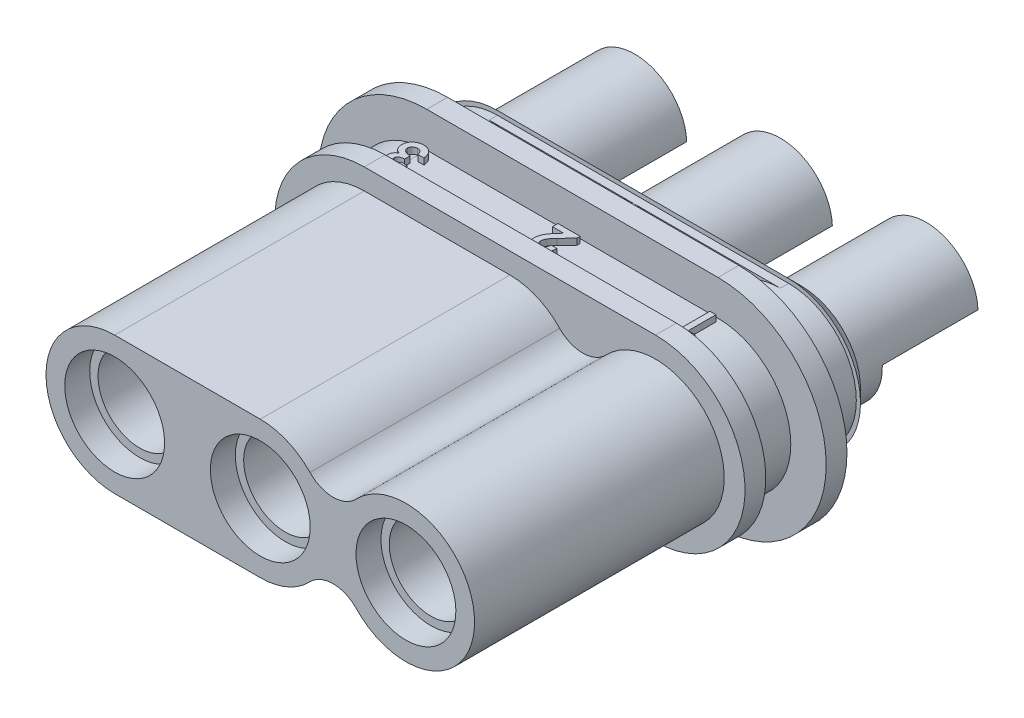
SolidWorks part; units mm, degrees
material "PA Type 6"
ref_plane "Front" through (0, 0, 0) normal (0, 0, 1) x (1, 0, 0)
ref_plane "Top" through (0, 0, 0) normal (0, 1, 0) x (1, 0, 0)
ref_plane "Side" through (0, 0, 0) normal (1, 0, 0) x (0, 0, -1)
ref_axis "Axis1" through (0, 0, 54.75) along (0, 0, -1)
sketch "Sketch1" plane through (0, 0, 0) normal (0, 0, 1) x (1, 0, 0)
  line L0 (-3.5, 0) -> (3.5, 0) construction
  line L1 (6.05, 0) -> (-6.05, 0) construction
  line L2 (-3.5, 1.65) -> (3.5, 1.65)
  line L3 (-3.5, -1.65) -> (3.5, -1.65)
  arc A0 (-3.5, 1.65) -> (-3.5, -1.65) centre (-3.5, 0) ccw
  arc A1 (3.5, -1.65) -> (3.5, 1.65) centre (3.5, 0) ccw
  point P5 (0, 0)
  dimension "D2" = 7
  dimension "D1" = 3.3
extrude "Boss-Extrude1" add sketch "Sketch1" along normal blind 6
sketch "Sketch2" plane through (0, 0, 0) normal (0, 0, 1) x (1, 0, 0)
  circle A0 centre (3.5, 0) radius 1.25
  circle A1 centre (0, 0) radius 1.25
  circle A2 centre (-3.5, 0) radius 1.25
  dimension "D1" = 2.5
sketch "Sketch3" plane through (0, 0, 6) normal (0, 0, 1) x (1, 0, 0)
  line L0 (3.5, 1.65) -> (-3.5, 1.65) construction
  line L1 (3.5, 1.65) -> (0, 1.65)
  line L2 (3.3, 0) -> (-3.3, 0) construction
  line L3 (0, 0) -> (7.6068, 0) construction
  line L4 (3.5, -1.65) -> (0, -1.65)
  arc A0 (3.5, 1.65) -> (2.3052, 1.1379) centre (3.5, 0) ccw
  arc A2 (1.1948, 1.1379) -> (0, 1.65) centre (0, 0) ccw
  arc A3 (1.1948, 1.1379) -> (2.3052, 1.1379) centre (1.75, 1.6667) ccw
  arc A4 (1.1948, -1.1379) -> (2.3052, -1.1379) centre (1.75, -1.6667) cw
  arc A5 (1.1948, -1.1379) -> (0, -1.65) centre (0, 0) cw
  arc A6 (3.5, -1.65) -> (2.3052, -1.1379) centre (3.5, 0) cw
  arc A7 (3.5, -1.65) -> (3.5, 1.65) centre (3.5, 0) ccw construction
  dimension "D1" = 0.7667
  dimension "D2" = 0.9
extrude "Cut-Extrude7" cut sketch "Sketch3" against normal through all
sketch "Sketch25" plane through (0, 0, 0) normal (0, 0, -1) x (-1, 0, 0)
  line L0 (-3.5, 0) -> (3.5, 0) construction
  line L1 (-3.5, 2.15) -> (3.5, 2.15)
  line L2 (-3.5, -2.15) -> (3.5, -2.15)
  arc A0 (-3.5, 2.15) -> (-3.5, -2.15) centre (-3.5, 0) ccw
  arc A1 (3.5, -2.15) -> (3.5, 2.15) centre (3.5, 0) ccw
  point P2 (0, 0)
  dimension "D1" = 4.3
extrude "Boss-Extrude14" add sketch "Sketch25" along normal blind 0.5
sketch "Sketch26" plane through (0, 0, -0.5) normal (0, 0, -1) x (-1, 0, 0)
  line L0 (-3.5, 0) -> (3.5, 0) construction
  line L1 (-3.5, 1.75) -> (3.5, 1.75)
  line L2 (-3.5, -1.75) -> (3.5, -1.75)
  arc A0 (-3.5, 1.75) -> (-3.5, -1.75) centre (-3.5, 0) ccw
  arc A1 (3.5, -1.75) -> (3.5, 1.75) centre (3.5, 0) ccw
  point P2 (0, 0)
  dimension "D1" = 3.5
extrude "Boss-Extrude15" add sketch "Sketch26" along normal blind 1
sketch "Sketch27" plane through (0, 0, -1.5) normal (0, 0, -1) x (-1, 0, 0)
  line L0 (-3.5, 0) -> (3.5, 0) construction
  line L1 (-3.5, 2.6) -> (3.5, 2.6)
  line L2 (-3.5, -2.6) -> (3.5, -2.6)
  arc A0 (-3.5, 2.6) -> (-3.5, -2.6) centre (-3.5, 0) ccw
  arc A1 (3.5, -2.6) -> (3.5, 2.6) centre (3.5, 0) ccw
  point P2 (0, 0)
  dimension "D1" = 5.2
extrude "Boss-Extrude16" add sketch "Sketch27" along normal blind 0.5
sketch "Sketch28" plane through (0, 0, -2) normal (0, 0, -1) x (-1, 0, 0)
  line L0 (-3.5, 0) -> (3.5, 0) construction
  line L1 (-3.5, 1.725) -> (3.5, 1.725)
  line L2 (-3.5, -1.725) -> (3.5, -1.725)
  arc A0 (-3.5, 1.725) -> (-3.5, -1.725) centre (-3.5, 0) ccw
  arc A1 (3.5, -1.725) -> (3.5, 1.725) centre (3.5, 0) ccw
  point P2 (0, 0)
  dimension "D1" = 3.45
extrude "Boss-Extrude17" add sketch "Sketch28" along normal blind 1.5
chamfer "Chamfer2" distance 0.3 angle 45 4 edges at (0, 1.725, -3.5) (-5.225, 0, -3.5) (0, -1.725, -3.5) (5.225, 0, -3.5)
sketch "Sketch29" plane through (0, 0, -2) normal (0, 0, -1) x (-1, 0, 0)
  line L4 (3.5, 1.625) -> (-3.5, 1.625)
  line L5 (-3.5, -1.625) -> (3.5, -1.625)
  line L6 (3.5, 1.625) -> (-3.5, 1.625)
  line L7 (-3.5, -1.625) -> (3.5, -1.625)
  line L8 (3.5, 1.725) -> (-3.5, 1.725)
  line L9 (-3.5, -1.725) -> (3.5, -1.725)
  line L10 (3.5, 1.725) -> (-3.5, 1.725)
  line L11 (-3.5, -1.725) -> (3.5, -1.725)
  arc A4 (3.5, -1.625) -> (3.5, 1.625) centre (3.5, 0) ccw
  arc A5 (-3.5, 1.625) -> (-3.5, -1.625) centre (-3.5, 0) ccw
  arc A6 (3.5, -1.625) -> (3.5, 1.625) centre (3.5, 0) ccw
  arc A7 (-3.5, 1.625) -> (-3.5, -1.625) centre (-3.5, 0) ccw
  arc A8 (3.5, -1.725) -> (3.5, 1.725) centre (3.5, 0) ccw
  arc A9 (-3.5, 1.725) -> (-3.5, -1.725) centre (-3.5, 0) ccw
  arc A10 (3.5, -1.725) -> (3.5, 1.725) centre (3.5, 0) ccw
  arc A11 (-3.5, 1.725) -> (-3.5, -1.725) centre (-3.5, 0) ccw
  dimension "D3" = 3.25
  dimension "D1" = 0.1
  dimension "D2" = 0
extrude "Cut-Extrude9" cut sketch "Sketch29" along normal up to vertex up to point (3.5, -1.725, -3.2)
sketch "Sketch35" plane through (0, 0, -2) normal (0, 0, -1) x (-1, 0, 0)
  line L5 (3.5, 1.625) -> (3.5, 2.6)
  line L10 (0, 1.625) -> (0, 2.6)
  line L11 (0, 2.6) -> (3.5, 2.6)
  line L12 (5.225, 0) -> (-5.225, 0) construction
  line L13 (3.5, 2.6) -> (-3.5, 2.6) construction
  circle A4 centre (3.5, 0) radius 1.25 construction
  circle A5 centre (0, 0) radius 1.25 construction
  arc A10 (1.2535, 1.034) -> (0, 1.625) centre (0, 0) ccw
  arc A11 (2.2465, 1.034) -> (1.2535, 1.034) centre (1.75, 1.4436) cw
  arc A12 (3.5, 1.625) -> (2.2465, 1.034) centre (3.5, 0) ccw
  arc A13 (3.5, -1.625) -> (3.5, 1.625) centre (3.5, 0) ccw construction
  dimension "D1" = 0.8
extrude "Cut-Extrude11" cut sketch "Sketch35" along normal offset from surface (1 mm away) 0.2 up to face at (0, 0, -3.2)
mirror "Mirror4" about plane through (0, 0, 0) normal (1, 0, 0) of "Cut-Extrude11"
mirror "Mirror5" about plane through (0, 0, 0) normal (0, 1, 0) of "Cut-Extrude11", "Mirror4"
ref_plane "Plane2" through (3.5, 0, 0) normal (1, 0, 0) x (0, 0, -1)
sketch "Sketch31" plane through (3.5, 0, 0) normal (1, 0, 0) x (0, 0, -1)
  line L0 (0, 0) -> (-7.12, 0) construction
  line L1 (0, 0) -> (3.5, 0) construction
  line L2 (-6, 0) -> (-6, 1.2)
  line L3 (-6, 1.65) -> (-6, -1.65) construction
  line L4 (-6, 1.2) -> (0.5, 1.2)
  line L5 (0.5, 1.2) -> (0.5, 1.25)
  line L6 (0.5, -1.75) -> (0.5, 1.75) construction
  line L7 (0.5, 1.25) -> (3.5, 1.25)
  line L8 (3.5, 1.25) -> (3.5, 0)
  line L9 (3.5, -1.425) -> (3.5, 1.425) construction
  line L10 (-6, 0) -> (3.5, 0)
  dimension "D3" = 2.5
  dimension "D1" = 6.5
  dimension "D2" = 2.4
revolve "Cut-Revolve1" cut sketch "Sketch31" angle 360 about L10
pattern_linear "LPattern4" count 3 spacing 3.5 along (-1, 0, 0) of "Cut-Revolve1"
sketch "Sketch32" plane through (3.5, 0, 0) normal (1, 0, 0) x (0, 0, -1)
  line L0 (-5.4, 1.2) -> (-5.4, 1)
  line L1 (-5.4, 1) -> (1.1, 1)
  line L3 (0.5, 1.2) -> (-6, 1.2) construction
  line L4 (0.5, 1.2) -> (-5.4, 1.2)
  line L5 (0, 0) -> (-6.3597, 0) construction
  line L6 (-6, 1.65) -> (-6, -1.65) construction
  line L8 (0.5, -1.25) -> (0.5, 1.25) construction
  line L9 (0.5, 1.2) -> (0.5, 1.25)
  line L10 (0.5, 1.25) -> (6.5, 1.25)
  line L12 (6.5, 1.25) -> (6.5, 0.7)
  line L13 (3.5, -1.425) -> (3.5, 1.425) construction
  line L14 (6.5, 0.7) -> (2.8, 0.7)
  line L15 (2.8, 0.7) -> (2.3794, 0)
  line L16 (1.7009, 0) -> (2.3794, 0)
  line L17 (1.1, 1) -> (1.7009, 0)
  dimension "D1" = 2
  dimension "D2" = 0.6
  dimension "D3" = 3
  dimension "D4" = 1.4
  dimension "D5" = 59
  dimension "D6" = 3.7
  dimension "D7" = 6.5
  dimension "D8" = 59
revolve "Revolve1" add sketch "Sketch32" angle 360 about L5
sketch "Sketch33" plane through (0, 0, 0) normal (1, 0, 0) x (0, 0, -1)
  line L0 (6.5, -1.25) -> (6.5, 1.25) construction
  line L1 (6.5, 0.05) -> (4.2, 0.05)
  line L2 (6.5, 0.05) -> (6.5, -1.25)
  line L3 (6.5, -1.25) -> (4.2, -1.25)
  line L4 (4.2, 0.05) -> (4.2, -1.25)
  line L5 (6.5, 1.25) -> (0.5, 1.25) construction
  dimension "D1" = 2.3
  dimension "D2" = 1.2
extrude "Cut-Extrude10" cut sketch "Sketch33" against normal through all both and the other way through all
pattern_linear "LPattern5" count 3 spacing 3.5 along (-1, 0, 0) of bodies 158
ref_plane "Plane3" through (0, 1.9, 0) normal (0, 1, 0) x (1, 0, 0)
sketch "Sketch38" plane through (0, 1.9, 0) normal (0, 1, 0) x (1, 0, 0)
  line L0 (-4.2497, 1.4) -> (-2.7503, 1.4) construction
  line L2 (-3.5, 1.5) -> (3.5, 1.5) construction
  line L4 (-0.9888, 1.4) -> (0.9888, 1.4) construction
  line L5 (2.4642, 1.4) -> (4.5358, 1.4) construction
  text T0 "1"
  text T1 "2"
  text T2 "3"
  point P19 (2.4642, 0.9)
  dimension "D1" = 0.1
extrude "Boss-Extrude18" add sketch "Sketch38" against normal blind 0.3
ref_plane "Plane4" through (0, -1.9, 0) normal (0, -1, 0) x (-1, 0, 0)
sketch "Sketch39" plane through (0, -1.9, 0) normal (0, -1, 0) x (-1, 0, 0)
  line L0 (-4.0045, 1.4) -> (-2.9955, 1.4) construction
  line L1 (-0.8219, 1.4) -> (0.8219, 1.4) construction
  line L2 (3.0253, 1.4) -> (3.9747, 1.4) construction
  line L4 (0, 2.86) -> (0, -2.86) construction
  line L7 (-3.5, 1.5) -> (3.5, 1.5) construction
  text T0 "3"
  text T1 "2"
  text T2 "1"
  point P9 (0, 1.4)
  point P15 (-4.0045, 1)
  dimension "D1" = 0.1
extrude "Boss-Extrude19" add sketch "Sketch39" against normal blind 0.3
